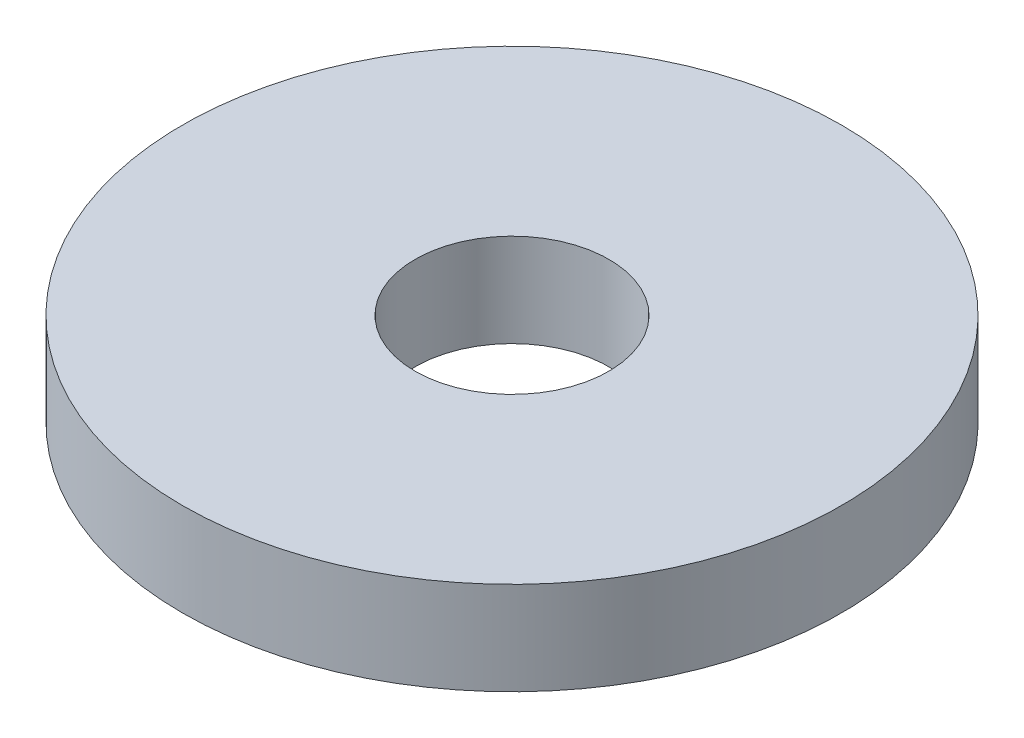
SolidWorks part; units mm, degrees
ref_plane "Front Plane" through (0, 0, 0) normal (0, 0, 1) x (1, 0, 0)
ref_plane "Top Plane" through (0, 0, 0) normal (0, 1, 0) x (1, 0, 0)
ref_plane "Right Plane" through (0, 0, 0) normal (1, 0, 0) x (0, 0, -1)
sketch "Sketch1" plane through (0, 0, 0) normal (0, 1, 0) x (1, 0, 0)
  circle A0 centre (0, 0) radius 85
  dimension "FLANGE_OD" = 170
extrude "Boss-Extrude1" add sketch "Sketch1" along normal blind 24
sketch "Sketch2" plane through (0, 0, 0) normal (0, 1, 0) x (1, 0, 0)
  circle A0 centre (0, 0) radius 25
  dimension "BORE_D" = 50
extrude "Cut-Extrude1" cut sketch "Sketch2" along normal through all
sketch "Sketch3" plane through (0, 24, 0) normal (0, 1, 0) x (1, 0, 0)
  circle A0 centre (0, 0) radius 16.2397 construction
  circle A1 centre (-16.2397, 0) radius 2.0223
  dimension "BOLT_D" = 4.0445
  dimension "BOLT_PCD" = 32.4794
extrude "Cut-Extrude2" cut sketch "Sketch3" against normal blind 17.1284 rebuild error yes
pattern_circular "CirPattern1" count 4 over 360 rebuild error yes
